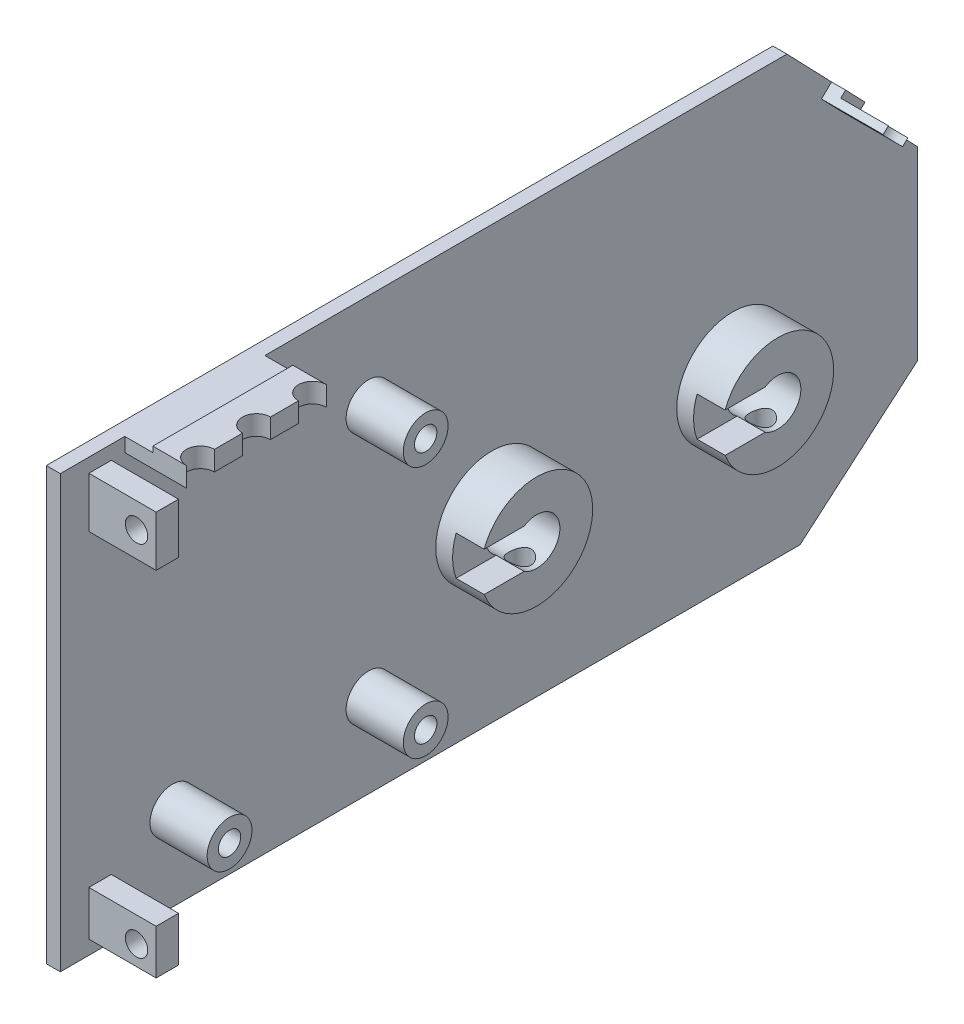
SolidWorks part; units mm, degrees
ref_plane "Front Plane" through (0, 0, 0) normal (0, 0, 1) x (1, 0, 0)
ref_plane "Top Plane" through (0, 0, 0) normal (0, 1, 0) x (1, 0, 0)
ref_plane "Right Plane" through (0, 0, 0) normal (1, 0, 0) x (0, 0, -1)
sketch "Sketch1" plane through (0, 0, 0) normal (1, 0, 0) x (0, 0, -1)
  line L0 (0, 0) -> (0, 77)
  line L1 (0, 77) -> (128, 77)
  line L2 (128, 77) -> (153, 51)
  line L3 (153, 51) -> (153, 18)
  line L4 (153, 18) -> (132, 0)
  line L5 (132, 0) -> (0, 0)
  dimension "D1" = 132
  dimension "D2" = 77
  dimension "D3" = 128
  dimension "D4" = 26
  dimension "D5" = 153
  dimension "D6" = 18
extrude "Base" add sketch "Sketch1" along normal blind 2.5
ref_plane "Middle" through (13.5, 0, 0) normal (1, 0, 0) x (0, 0, -1)
sketch "Sketch2" plane through (2.5, 0, 0) normal (1, 0, 0) x (0, 0, -1)
  circle A0 centre (20, 15) radius 4
  circle A1 centre (55, 15) radius 4
  circle A2 centre (55, 60) radius 4
  circle A3 centre (20, 15) radius 2
  circle A4 centre (55, 15) radius 2
  circle A5 centre (55, 60) radius 2
  dimension "D1" = 8
  dimension "D2" = 4
  dimension "D3" = 20
  dimension "D4" = 15
  dimension "D5" = 55
  dimension "D6" = 60
  dimension "D7" = 55
extrude "PCB_Mounts" add sketch "Sketch2" along normal blind 10.2
ref_plane "Plane1" through (0, 32, 0) normal (0, 1, 0) x (1, 0, 0)
sketch "Sketch3" plane through (2.5, 0, 0) normal (1, 0, 0) x (0, 0, -1)
  line L0 (5.775, 32) -> (-5.775, 32) construction
  circle A0 centre (77, 32) radius 4.15
  circle A1 centre (120, 32) radius 4.15
  circle A2 centre (77, 32) radius 10
  circle A3 centre (120, 32) radius 10
  dimension "D3" = 8.3
  dimension "D4" = 20
  dimension "D1" = 77
  dimension "D2" = 120
extrude "Boss-Extrude3" add sketch "Sketch3" along normal blind 8
sketch "Sketch4" plane through (10.5, 0, 0) normal (1, 0, 0) x (0, 0, -1)
  line L1 (74.7701, 35.5) -> (67, 35.5)
  line L2 (74.7701, 35.5) -> (74.7701, 28.5)
  line L3 (74.7701, 28.5) -> (67, 28.5)
  line L4 (67, 35.5) -> (67, 28.5)
  line L5 (117.7701, 35.5) -> (110, 35.5)
  line L6 (117.7701, 35.5) -> (117.7701, 28.5)
  line L7 (117.7701, 28.5) -> (110, 28.5)
  line L8 (110, 35.5) -> (110, 28.5)
  circle A0 centre (77, 32) radius 4.15 construction
  circle A1 centre (77, 32) radius 10 construction
  circle A2 centre (120, 32) radius 4.15 construction
  circle A3 centre (120, 32) radius 10 construction
  dimension "D1" = 7
extrude "Cut-Extrude1" cut sketch "Sketch4" against normal blind 5
ref_axis "Axis1" through (10.5, 32, -77) along (-1, 0, 0)
ref_axis "Axis2" through (10.5, 32, -120) along (-1, 0, 0)
sketch "Sketch5" plane through (0, 32, 0) normal (0, 1, 0) x (1, 0, 0)
  line L2 (10.5, 77) -> (2.5, 77) construction
  line L3 (10.5, 120) -> (2.5, 120) construction
  line L4 (10.5, 67.6325) -> (10.5, 87) construction
  circle A0 centre (7.5, 77) radius 2
  circle A1 centre (7.5, 120) radius 2
  dimension "D1" = 4
  dimension "D2" = 3
extrude "Cut-Extrude2" cut sketch "Sketch5" against normal through all
sketch "Sketch13" plane through (0, 77, 0) normal (0, 1, 0) x (1, 0, 0)
  line L1 (13.5, 11.5) -> (2.5, 11.5)
  line L2 (13.5, 11.5) -> (13.5, 36.5)
  line L3 (13.5, 36.5) -> (2.5, 36.5)
  line L4 (2.5, 11.5) -> (2.5, 36.5)
  line L5 (13.5, 11.5) -> (2.5, 36.5) construction
  line L6 (13.5, 36.5) -> (2.5, 11.5) construction
  line L7 (2.5, 128) -> (2.5, 0) construction
  line L8 (13.5, -42.35) -> (13.5, 42.35) construction
  point P0 (8, 24)
  dimension "D1" = 24
  dimension "D2" = 25
extrude "Boss-Extrude8" add sketch "Sketch13" against normal blind 2.5
sketch "Sketch15" plane through (0, 77, 0) normal (0, 1, 0) x (1, 0, 0)
  line L0 (13.5, 11.5) -> (13.5, 36.5) construction
  line L1 (13.5, 11.5) -> (7.5, 11.5)
  line L2 (13.5, 11.5) -> (13.5, 36.5)
  line L3 (13.5, 36.5) -> (7.5, 36.5)
  line L4 (7.5, 11.5) -> (7.5, 36.5)
  point P6 (13.5, 24)
  point P7 (13.5, 24)
  dimension "D1" = 6
  dimension "D2" = 25
extrude "Boss-Extrude9" add sketch "Sketch15" along normal blind 1 and the other way blind 2.5
sketch "Sketch16" plane through (0, 78, 0) normal (0, 1, 0) x (1, 0, 0)
  line L0 (13.5, 11.5) -> (13.5, 36.5) construction
  circle A0 centre (13.5, 24) radius 2.5
  circle A1 centre (13.5, 34) radius 2.5
  circle A2 centre (13.5, 14) radius 2.5
  dimension "D3" = 5
  dimension "D1" = 10
  dimension "D2" = 10
extrude "Cut-Extrude4" cut sketch "Sketch16" against normal up to next
sketch "Sketch9" plane through (0, 0, 0) normal (-1, 0, 0) x (0, 0, 1)
  line L0 (-128, 77) -> (-129.6647, 77)
  line L1 (-129.6647, 77) -> (-141.101, 65.1063)
  line L2 (-141.101, 65.1063) -> (-140.236, 64.2745)
  line L3 (-153, 51) -> (-128, 77) construction
  line L4 (-140.236, 64.2745) -> (-128, 77)
  dimension "D1" = 1.2
  dimension "D2" = 16.5
extrude "Boss-Extrude5" add sketch "Sketch9" against normal up to vertex (2.5 mm away) up to point (2.5, 77, -128)
sketch "Sketch10" plane through (2.5, 0, 0) normal (1, 0, 0) x (0, 0, -1)
  line L0 (141.101, 65.1063) -> (137.6355, 68.7104)
  line L1 (141.101, 65.1063) -> (139.299, 63.3735)
  line L2 (137.6355, 68.7104) -> (135.8334, 66.9776)
  line L3 (139.299, 63.3735) -> (135.8334, 66.9776)
  line L4 (129.6647, 77) -> (141.101, 65.1063) construction
  dimension "D1" = 2.5
  dimension "D2" = 5
extrude "Boss-Extrude6" add sketch "Sketch10" along normal blind 2.5
sketch "Sketch12" plane through (0, 100.0405, -104.0422) normal (0, -0.6931, 0.7208) x (1, 0, 0)
  line L0 (5, -45.8676) -> (5, -50.8676)
  line L1 (5, -45.8676) -> (13.5, -45.8676)
  line L2 (5, -50.8676) -> (13.5, -50.8676)
  line L4 (0, -69.2831) -> (0, -50.8676) construction
  arc A0 (13.5, -45.8676) -> (13.5, -50.8676) centre (13.5, -48.3676) ccw
  dimension "D1" = 2.5
  dimension "D2" = 13.5
extrude "Boss-Extrude7" add sketch "Sketch12" against normal blind 1.3
ref_plane "Screw_Mounts" through (11, 0, 0) normal (1, 0, 0) x (0, 0, -1)
sketch "Sketch17" plane through (2.5, 0, 0) normal (1, 0, 0) x (0, 0, -1)
  line L0 (0, 77) -> (0, 0) construction
  line L1 (5.1, 74.5) -> (9.1, 74.5)
  line L2 (5.1, 74.5) -> (5.1, 65.5)
  line L3 (5.1, 65.5) -> (9.1, 65.5)
  line L4 (9.1, 74.5) -> (9.1, 65.5)
  line L5 (5.1, 10.5) -> (9.1, 10.5)
  line L6 (5.1, 10.5) -> (5.1, 2.5)
  line L7 (5.1, 2.5) -> (9.1, 2.5)
  line L8 (9.1, 10.5) -> (9.1, 2.5)
  line L9 (11.5, 77) -> (0, 77) construction
  dimension "D1" = 5.1
  dimension "D2" = 2.5
  dimension "D3" = 8
  dimension "D4" = 4
  dimension "D5" = 2.5
  dimension "D6" = 9
extrude "Boss-Extrude10" add sketch "Sketch17" along normal blind 12
sketch "Sketch18" plane through (0, 0, -5.1) normal (0, 0, 1) x (1, 0, 0)
  line L0 (11, -5.0397) -> (11, 5.0397) construction
  circle A0 centre (11, 6) radius 2
  circle A1 centre (11, 70) radius 2
  dimension "D3" = 4
  dimension "D1" = 6
  dimension "D2" = 70
extrude "Cut-Extrude5" cut sketch "Sketch18" against normal up to next
equation "\"D2@Sketch16\"=\"D1@Sketch16\""
